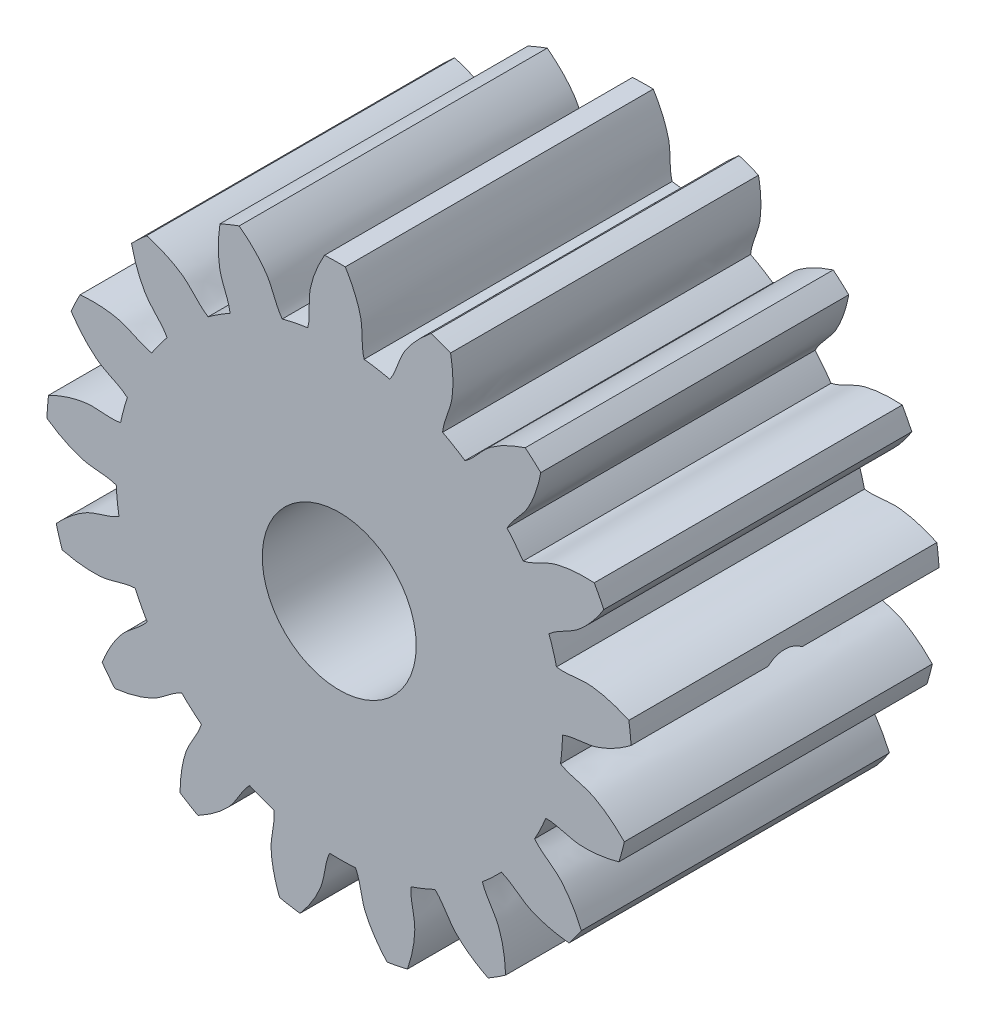
SolidWorks part; units mm, degrees
ref_plane "前视基准面" through (0, 0, 0) normal (0, 0, 1) x (1, 0, 0)
ref_plane "上视基准面" through (0, 0, 0) normal (0, 1, 0) x (1, 0, 0)
ref_plane "右视基准面" through (0, 0, 0) normal (1, 0, 0) x (0, 0, -1)
sketch "草图1" plane through (0, 0, 0) normal (0, 0, 1) x (1, 0, 0)
  circle A0 centre (0, 0) radius 14.5
  circle A1 centre (0, 0) radius 5
  dimension "D1" = 10
  dimension "D2" = 29
extrude "凸台-拉伸1" add sketch "草图1" along normal blind 20
sketch "草图2" plane through (0, 0, 0) normal (0, 0, 1) x (1, 0, 0)
  arc A0 (18.8067, 2.7036) -> (18.951, 1.3635) centre (0, 0) cw
  arc A1 (14.1058, 3.3579) -> (14.4974, -0.2769) centre (0, 0) cw
  spline S0 degree 3 poles (18.951, 1.3635) (18.5795, 1.0858) (18.0039, 0.708) (17.1929, 0.3216) (16.1208, -0.082) (15.1602, -0.0216) (14.4974, -0.2769) knots 0 0 0 0 0.289468 0.427045 0.559834 1 1 1 1
  spline S1 degree 3 poles (18.8067, 2.7036) (18.3845, 2.8959) (17.7417, 3.1424) (16.867, 3.3473) (15.7335, 3.5133) (14.8079, 3.2497) (14.1058, 3.3579) knots 0 0 0 0 0.289468 0.427045 0.559834 1 1 1 1
extrude "凸台-拉伸2" add sketch "草图2" along normal blind 20
pattern_circular "阵列(圆周)1" count 17 over 360 about axis through (0, 0, 20) along (0, 0, -1) of "凸台-拉伸2"
sketch "草图5" plane through (0, 0, 0) normal (1, 0, 0) x (0, 0, -1)
  line L0 (-20, 18.996) -> (0, 18.996) construction
  circle A0 centre (-10, 0) radius 1.75
  point P2 (0, 0)
  point P4 (-9.5793, 0)
  point P7 (-10, 18.996)
  dimension "D1" = 3.5
extrude "切除-拉伸1" cut sketch "草图5" against normal mid plane 100
